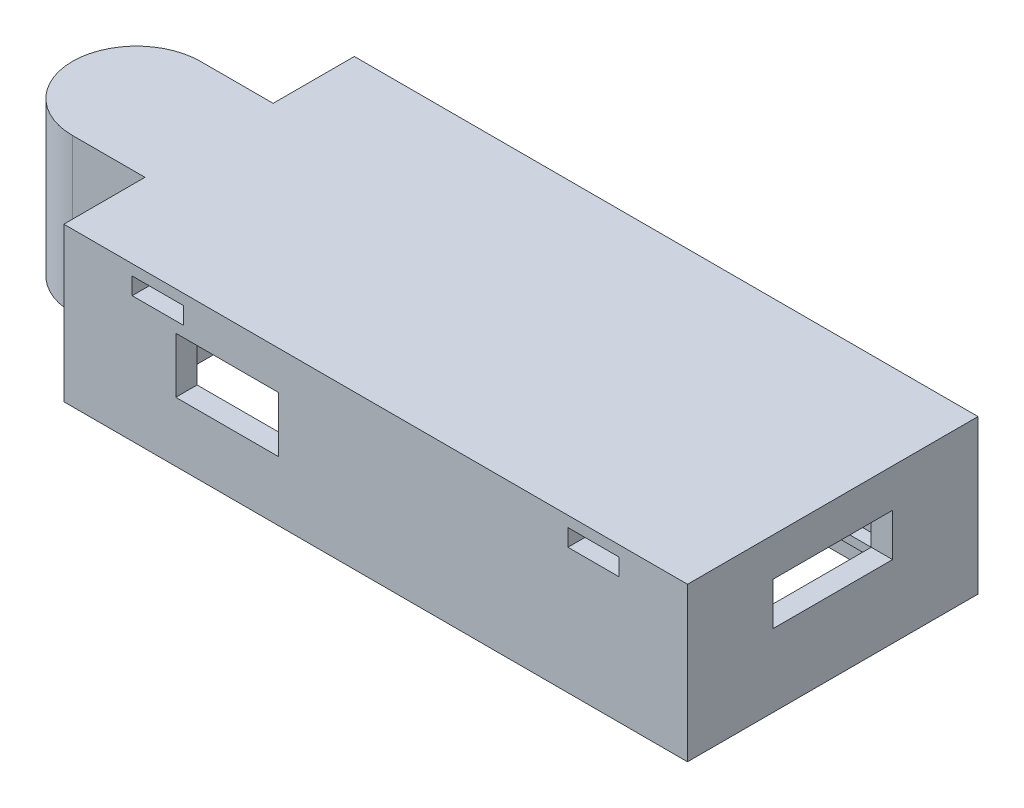
SolidWorks part; units mm, degrees
ref_plane "Front Plane" through (0, 0, 0) normal (0, 0, 1) x (1, 0, 0)
ref_plane "Top Plane" through (0, 0, 0) normal (0, 1, 0) x (1, 0, 0)
ref_plane "Right Plane" through (0, 0, 0) normal (1, 0, 0) x (0, 0, -1)
sketch "Sketch1" plane through (0, 0, 0) normal (0, 1, 0) x (1, 0, 0)
  line L1 (-31.2084, 17.8232) -> (41.7916, 17.8232)
  line L2 (-31.2084, 17.8232) -> (-31.2084, -16.1768)
  line L3 (-31.2084, -16.1768) -> (41.7916, -16.1768)
  line L4 (41.7916, 17.8232) -> (41.7916, -16.1768)
  dimension "D1" = 73
  dimension "D2" = 34
extrude "base" add sketch "Sketch1" along normal blind 4.5
sketch "Sketch21" plane through (0, 0, 0) normal (0, -1, 0) x (-1, 0, 0)
  line L11 (-41.7916, 17.8232) -> (31.2084, 17.8232)
  line L12 (-41.7916, 17.8232) -> (-41.7916, -16.1768)
  line L13 (-41.7916, -16.1768) -> (31.2084, -16.1768)
  line L14 (31.2084, 17.8232) -> (31.2084, -16.1768)
extrude "extrude up" add sketch "Sketch21" along normal blind 13.5
sketch "Sketch22" plane through (0, -13.5, 0) normal (0, -1, 0) x (-1, 0, 0)
  line L0 (-41.7916, 17.8232) -> (-41.7916, -16.1768) construction
  line L1 (-39.2916, 15.3232) -> (28.7084, 15.3232)
  line L2 (-39.2916, 15.3232) -> (-39.2916, -13.6768)
  line L3 (-39.2916, -13.6768) -> (28.7084, -13.6768)
  line L4 (28.7084, 15.3232) -> (28.7084, -13.6768)
  line L5 (31.2084, 17.8232) -> (-41.7916, 17.8232) construction
  line L6 (31.2084, -16.1768) -> (31.2084, 17.8232) construction
  line L7 (-41.7916, -16.1768) -> (31.2084, -16.1768) construction
  dimension "D1" = 2.5
  dimension "D2" = 2.5
  dimension "D3" = 2.5
  dimension "D4" = 2.5
extrude "cut down" cut sketch "Sketch22" against normal blind 13.5
sketch "Sketch27" plane through (0, 0, 0) normal (0, -1, 0) x (1, 0, 0)
  line L0 (-28.7084, -15.3232) -> (39.2916, -15.3232) construction
  line L1 (39.2916, -15.3232) -> (39.2916, 13.6768) construction
  circle A0 centre (31.1416, -11.9232) radius 2
  dimension "D1" = 4
  dimension "D2" = 3.4
  dimension "D3" = 8.15
extrude "Boss-Extrude15" add sketch "Sketch27" along normal blind 1.5 contours A0
sketch "Sketch28" plane through (0, 0, 0) normal (0, -1, 0) x (1, 0, 0)
  line L0 (39.2916, -15.3232) -> (39.2916, 13.6768) construction
  line L1 (39.2916, 13.6768) -> (-28.7084, 13.6768) construction
  circle A0 centre (31.1416, 10.2768) radius 2
  dimension "D1" = 4
  dimension "D2" = 8.15
  dimension "D3" = 3.4
sketch "Sketch29" plane through (0, 0, 0) normal (0, -1, 0) x (1, 0, 0)
  line L0 (-28.7084, -15.3232) -> (39.2916, -15.3232) construction
  circle A0 centre (9.0416, -11.9232) radius 2
  circle A1 centre (31.1416, -11.9232) radius 2 construction
  dimension "D1" = 4
  dimension "D2" = 3.4
  dimension "D3" = 22.1
sketch "Sketch30" plane through (0, 0, 0) normal (0, -1, 0) x (1, 0, 0)
  line L0 (39.2916, 13.6768) -> (-28.7084, 13.6768) construction
  circle A0 centre (9.0416, 10.2768) radius 2
  circle A1 centre (31.1416, 10.2768) radius 2 construction
  dimension "D1" = 4
  dimension "D2" = 3.4
  dimension "D3" = 22.1
extrude "Boss-Extrude16" add sketch "Sketch29" along normal blind 1.5 contours A0
extrude "Boss-Extrude17" add sketch "Sketch30" along normal blind 1.5 contours A0
extrude "Boss-Extrude18" add sketch "Sketch28" along normal blind 1.5 contours A0
sketch "Sketch31" plane through (0, -1.5, 0) normal (0, -1, 0) x (1, 0, 0)
  circle A0 centre (31.1416, -11.9232) radius 1.5
  dimension "D1" = 3
extrude "Boss-Extrude19" add sketch "Sketch31" along normal blind 2
sketch "Sketch32" plane through (0, -1.5, 0) normal (0, -1, 0) x (1, 0, 0)
  circle A0 centre (9.0416, -11.9232) radius 1.5
  circle A1 centre (9.0416, -11.9232) radius 2 construction
  dimension "D1" = 3
  dimension "D2" = 0
extrude "Boss-Extrude20" add sketch "Sketch32" along normal blind 2
sketch "Sketch33" plane through (0, -1.5, 0) normal (0, -1, 0) x (1, 0, 0)
  circle A0 centre (9.0416, 10.2768) radius 1.5
  dimension "D1" = 3
extrude "Boss-Extrude21" add sketch "Sketch33" along normal blind 2
sketch "Sketch34" plane through (0, -1.5, 0) normal (0, -1, 0) x (1, 0, 0)
  circle A0 centre (31.1416, 10.2768) radius 1.5
  dimension "D1" = 3
extrude "Boss-Extrude22" add sketch "Sketch34" along normal blind 2
sketch "Sketch39" plane through (0, 0, -15.3232) normal (0, 0, 1) x (1, 0, 0)
  line L0 (-28.7084, 0) -> (-28.7084, -13.5) construction
  line L1 (-2.2084, -5.5) -> (-21.2084, -5.5)
  line L2 (-2.2084, -5.5) -> (-2.2084, -4.2)
  line L3 (-2.2084, -4.2) -> (-21.2084, -4.2)
  line L4 (-21.2084, -5.5) -> (-21.2084, -4.2)
  line L5 (-28.7084, 0) -> (39.2916, 0) construction
  dimension "D1" = 7.5
  dimension "D2" = 1.3
  dimension "D3" = 4.2
  dimension "D4" = 19
extrude "wall slit" cut sketch "Sketch39" against normal blind 1.5
sketch "Sketch41" plane through (0, 0, 0) normal (0, -1, 0) x (1, 0, 0)
  line L0 (-28.7084, 13.6768) -> (-28.7084, -15.3232) construction
  line L1 (-28.7084, -12.8232) -> (-26.2084, -12.8232)
  line L2 (-28.7084, -12.8232) -> (-28.7084, 11.1768)
  line L3 (-28.7084, 11.1768) -> (-26.2084, 11.1768)
  line L4 (-26.2084, -12.8232) -> (-26.2084, 11.1768)
  line L5 (-28.7084, -15.3232) -> (39.2916, -15.3232) construction
  line L6 (39.2916, 13.6768) -> (-28.7084, 13.6768) construction
  dimension "D1" = 2.5
  dimension "D2" = 2.5
  dimension "D3" = 2.5
extrude "outside block" add sketch "Sketch41" along normal blind 5
sketch "Sketch44" plane through (0, 0, 0) normal (0, -1, 0) x (1, 0, 0)
  line L0 (-28.7084, -15.3232) -> (39.2916, -15.3232) construction
  line L1 (5.2916, -12.8232) -> (2.7916, -12.8232)
  line L2 (5.2916, -12.8232) -> (5.2916, 11.1768)
  line L3 (5.2916, 11.1768) -> (2.7916, 11.1768)
  line L4 (2.7916, -12.8232) -> (2.7916, 11.1768)
  line L5 (39.2916, 13.6768) -> (-28.7084, 13.6768) construction
  line L6 (-26.2084, -12.8232) -> (-26.2084, 11.1768) construction
  dimension "D1" = 2.5
  dimension "D2" = 2.5
  dimension "D3" = 2.5
  dimension "D4" = 29
extrude "inside block" add sketch "Sketch44" along normal blind 5
sketch "Sketch45" plane through (0, 0, 13.6768) normal (0, 0, -1) x (-1, 0, 0)
  line L0 (-39.2916, 0) -> (28.7084, 0) construction
  line L1 (18.1084, 0) -> (6.1084, 0)
  line L2 (18.1084, 0) -> (18.1084, -6.5)
  line L3 (18.1084, -6.5) -> (6.1084, -6.5)
  line L4 (6.1084, 0) -> (6.1084, -6.5)
  line L5 (28.7084, 0) -> (28.7084, -13.5) construction
  dimension "D1" = 12
  dimension "D2" = 6.5
  dimension "D3" = 10.6
extrude "usb hole" cut sketch "Sketch45" against normal blind 2.5
sketch "Sketch62" plane through (0, -13.5, 0) normal (0, -1, 0) x (1, 0, 0)
  line L0 (41.7916, -17.8232) -> (41.7916, 16.1768) construction
  line L1 (40.2916, -16.3232) -> (-29.7084, -16.3232)
  line L2 (40.2916, -16.3232) -> (40.2916, 14.6768)
  line L3 (40.2916, 14.6768) -> (-29.7084, 14.6768)
  line L4 (-29.7084, -16.3232) -> (-29.7084, 14.6768)
  line L5 (-31.2084, -17.8232) -> (41.7916, -17.8232) construction
  line L6 (41.7916, 16.1768) -> (-31.2084, 16.1768) construction
  line L7 (-31.2084, 16.1768) -> (-31.2084, -17.8232) construction
  dimension "D1" = 1.5
  dimension "D2" = 1.5
  dimension "D3" = 1.5
  dimension "D4" = 1.5
extrude "raise lip" add sketch "Sketch62" along normal blind 1.5
sketch "Sketch63" plane through (0, -15, 0) normal (0, -1, 0) x (1, 0, 0)
  line L0 (40.2916, -16.3232) -> (40.2916, 14.6768) construction
  line L1 (39.2916, -15.3232) -> (-28.7084, -15.3232)
  line L2 (39.2916, -15.3232) -> (39.2916, 13.6768)
  line L3 (39.2916, 13.6768) -> (-28.7084, 13.6768)
  line L4 (-28.7084, -15.3232) -> (-28.7084, 13.6768)
  line L5 (-29.7084, -16.3232) -> (40.2916, -16.3232) construction
  line L6 (40.2916, 14.6768) -> (-29.7084, 14.6768) construction
  line L7 (-29.7084, 14.6768) -> (-29.7084, -16.3232) construction
  dimension "D1" = 1
  dimension "D2" = 1
  dimension "D3" = 1
  dimension "D4" = 1
extrude "cut lip" cut sketch "Sketch63" against normal blind 1.5
sketch "Sketch47" plane through (0, 0, 16.1768) normal (0, 0, 1) x (1, 0, 0)
  line L0 (-31.2084, 4.5) -> (41.7916, 4.5) construction
  line L1 (27.7916, 3.25) -> (33.7916, 3.25)
  line L2 (27.7916, 3.25) -> (27.7916, 1.25)
  line L3 (27.7916, 1.25) -> (33.7916, 1.25)
  line L4 (33.7916, 3.25) -> (33.7916, 1.25)
  line L5 (41.7916, 4.5) -> (41.7916, -13.5) construction
  dimension "D1" = 1.25
  dimension "D2" = 2
  dimension "D3" = 6
  dimension "D4" = 8
extrude "top tie hole" cut sketch "Sketch47" against normal blind 34
sketch "Sketch48" plane through (0, 0, 16.1768) normal (0, 0, 1) x (1, 0, 0)
  line L0 (-31.2084, 4.5) -> (41.7916, 4.5) construction
  line L1 (-23.2084, 3.25) -> (-17.2084, 3.25)
  line L2 (-23.2084, 3.25) -> (-23.2084, 1.25)
  line L3 (-23.2084, 1.25) -> (-17.2084, 1.25)
  line L4 (-17.2084, 3.25) -> (-17.2084, 1.25)
  line L5 (-31.2084, 4.5) -> (-31.2084, -13.5) construction
  dimension "D1" = 6
  dimension "D2" = 2
  dimension "D3" = 1.25
  dimension "D4" = 8
extrude "bottom tie hole" cut sketch "Sketch48" against normal blind 34
sketch "Sketch56" plane through (39.2916, 0, 0) normal (-1, 0, 0) x (0, 0, 1)
  line L0 (-15.3232, 0) -> (-15.3232, -15) construction
  line L1 (6.1768, -5) -> (-7.8232, -5)
  line L2 (6.1768, -5) -> (6.1768, 0)
  line L3 (6.1768, 0) -> (-7.8232, 0)
  line L4 (-7.8232, -5) -> (-7.8232, 0)
  line L5 (-15.3232, 0) -> (13.6768, 0) construction
  dimension "D1" = 14
  dimension "D2" = 7.5
  dimension "D3" = 5
extrude "wire hole" cut sketch "Sketch56" against normal blind 2.5
sketch "Sketch68" plane through (0, 0, -15.3232) normal (0, 0, 1) x (1, 0, 0)
  line L0 (39.2916, 0) -> (39.2916, -15) construction
  line L1 (39.2916, -12) -> (-28.7084, -12)
  line L2 (39.2916, -12) -> (39.2916, -11)
  line L3 (39.2916, -11) -> (-28.7084, -11)
  line L4 (-28.7084, -12) -> (-28.7084, -11)
  line L5 (-28.7084, 0) -> (-28.7084, -15) construction
  line L6 (-28.7084, -15) -> (39.2916, -15) construction
  dimension "D1" = 3
  dimension "D2" = 1
extrude "right ledge" add sketch "Sketch68" along normal blind 1.5
sketch "Sketch67" plane through (0, 0, 13.6768) normal (0, 0, -1) x (-1, 0, 0)
  line L0 (28.7084, 0) -> (28.7084, -15) construction
  line L1 (28.7084, -12) -> (-39.2916, -12)
  line L2 (28.7084, -12) -> (28.7084, -11)
  line L3 (28.7084, -11) -> (-39.2916, -11)
  line L4 (-39.2916, -12) -> (-39.2916, -11)
  line L5 (-39.2916, 0) -> (-39.2916, -15) construction
  line L6 (-39.2916, -15) -> (28.7084, -15) construction
  dimension "D1" = 1
  dimension "D2" = 3
extrude "left ledge" add sketch "Sketch67" along normal blind 1.5
sketch "Sketch65" plane through (0, -13.5, 0) normal (0, -1, 0) x (1, 0, 0)
  line L0 (-31.2084, 16.1768) -> (-31.2084, -17.8232) construction
  line L1 (-31.2084, -8.3232) -> (-47.2084, -8.3232)
  line L2 (-31.2084, -8.3232) -> (-31.2084, 6.6768)
  line L3 (-31.2084, 6.6768) -> (-47.2084, 6.6768)
  line L4 (-47.2084, -8.3232) -> (-47.2084, 6.6768)
  line L5 (41.7916, 16.1768) -> (-31.2084, 16.1768) construction
  dimension "D1" = 16
  dimension "D2" = 15
  dimension "D3" = 9.5
extrude "nut hole square" add sketch "Sketch65" against normal blind 18
fillet "nut hole fillet" radius 7.5 2 edges at (-47.2084, -4.5, -8.3232) (-47.2084, -4.5, 6.6768)
sketch "Sketch66" plane through (0, -13.5, 0) normal (0, -1, 0) x (1, 0, 0)
  line L1 (-35.0281, 5.5513) -> (-42.3887, 5.5513)
  line L2 (-42.3887, 5.5513) -> (-46.0691, -0.8232)
  line L3 (-46.0691, -0.8232) -> (-42.3887, -7.1977)
  line L4 (-42.3887, -7.1977) -> (-35.0281, -7.1977)
  line L5 (-35.0281, -7.1977) -> (-31.3478, -0.8232)
  line L6 (-31.3478, -0.8232) -> (-35.0281, 5.5513)
  line L7 (-31.2084, 6.6768) -> (-39.7084, 6.6768) construction
  line L8 (-29.7084, 14.6768) -> (-29.7084, -16.3232) construction
  circle A0 centre (-38.7084, -0.8232) radius 6.3745 construction
  dimension "D1" = 7.5
  dimension "D2" = 9
extrude "nut hole hex" cut sketch "Sketch66" against normal blind 15
sketch "Sketch69" plane through (0, 0, -15.3232) normal (0, 0, 1) x (1, 0, 0)
  line L0 (39.2916, -11) -> (-28.7084, -11) construction
  line L1 (34.2916, -10) -> (23.2916, -10)
  line L2 (34.2916, -10) -> (34.2916, -4)
  line L3 (34.2916, -4) -> (23.2916, -4)
  line L4 (23.2916, -10) -> (23.2916, -4)
  line L5 (39.2916, 0) -> (39.2916, -11) construction
  dimension "D1" = 11
  dimension "D2" = 6
  dimension "D3" = 1
  dimension "D4" = 5
extrude "Cut-Extrude1" cut sketch "Sketch69" against normal blind 2.5
sketch "Sketch70" plane through (0, 0, -15.3232) normal (0, 0, 1) x (1, 0, 0)
  line L0 (23.2916, -4) -> (23.2916, -10) construction
  line L1 (23.2916, -10) -> (34.2916, -10) construction
  circle A0 centre (13.2916, -7) radius 2.5
  point P4 (23.2916, -7)
  dimension "D1" = 5
  dimension "D2" = 10
  dimension "D3" = 3
extrude "Cut-Extrude2" cut sketch "Sketch70" against normal blind 2.5
